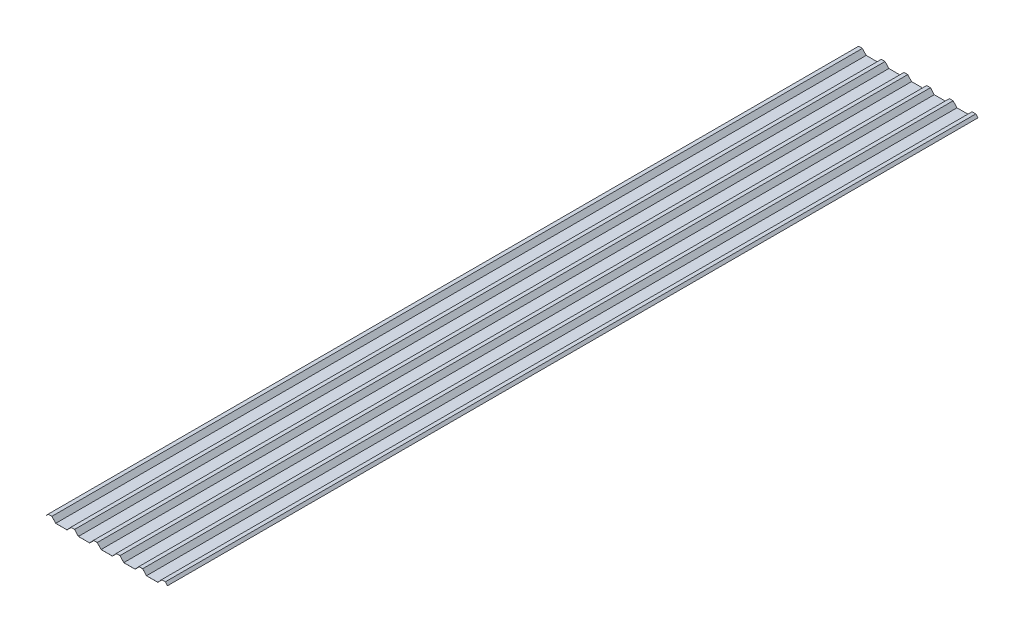
SolidWorks part; units mm, degrees
material "Alumina"
ref_plane "Plano frontal" through (0, 0, 0) normal (0, 0, 1) x (1, 0, 0)
ref_plane "Plano superior" through (0, 0, 0) normal (0, 1, 0) x (1, 0, 0)
ref_plane "Plano direito" through (0, 0, 0) normal (1, 0, 0) x (0, 0, -1)
sketch "Esboço1" plane through (0, 0, 0) normal (0, 0, 1) x (1, 0, 0)
  line L0 (0, 0) -> (32, 0)
  line L1 (65, -36) -> (163, -36)
  line L3 (0, 0) -> (-33, -36)
  line L4 (32, 0) -> (65, -36)
  line L5 (196, 0) -> (228, 0)
  line L6 (261, -36) -> (359, -36)
  line L7 (196, 0) -> (163, -36)
  line L8 (228, 0) -> (261, -36)
  line L9 (-33, -36) -> (-131, -36)
  line L10 (392, 0) -> (424, 0)
  line L11 (457, -36) -> (555, -36)
  line L12 (392, 0) -> (359, -36)
  line L13 (424, 0) -> (457, -36)
  line L14 (588, 0) -> (620, 0)
  line L15 (653, -36) -> (751, -36)
  line L16 (588, 0) -> (555, -36)
  line L17 (620, 0) -> (653, -36)
  line L18 (-196, 0) -> (-164, 0)
  line L19 (-196, 0) -> (-214.2729, -20)
  line L20 (-164, 0) -> (-131, -36)
  line L23 (784, 0) -> (816, 0)
  line L24 (784, 0) -> (751, -36)
  line L25 (816, 0) -> (834.5668, -20)
  point P8 (16, -36)
  point P12 (212, -36)
  point P18 (408, -36)
  point P23 (604, -36)
  dimension "D1" = 98
  dimension "D2" = 98
extrude "Extrusão-Fina1" add sketch "Esboço1" along normal blind 7000 thin contours L19 L18 L20 L9 L3 L0 L4 L1 L7 L5 L8 L6 L12 L10 L13 L11 L16 L14 L17 L15 L24 L23 L25 thin type one direction wall 0.5
